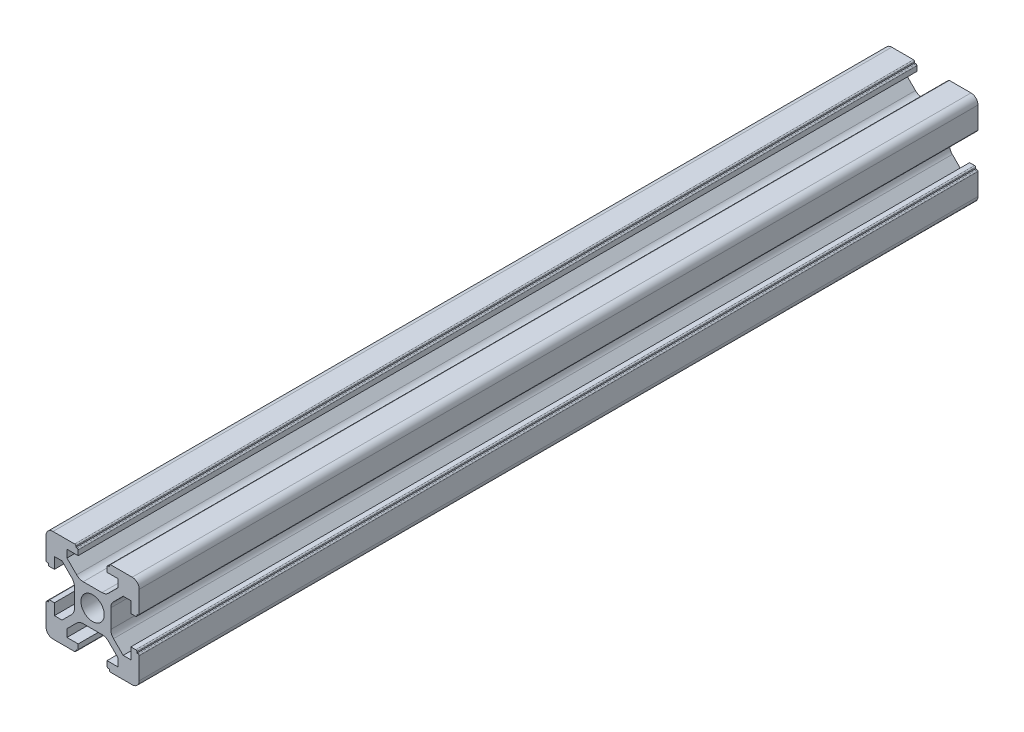
SolidWorks part; units mm, degrees
ref_plane "Front Plane" through (0, 0, 0) normal (0, 0, 1) x (1, 0, 0)
ref_plane "Top Plane" through (0, 0, 0) normal (0, 1, 0) x (1, 0, 0)
ref_plane "Right Plane" through (0, 0, 0) normal (1, 0, 0) x (0, 0, -1)
sketch "Sketch1" plane through (0, 0, 0) normal (0, 0, 1) x (1, 0, 0)
  line L0 (0, 0) -> (-10, 10) construction
  line L5 (0, 0) -> (10, 10) construction
  line L6 (22.7721, 0) -> (-22.7721, 0) construction
  line L7 (-8.5, 10) -> (-3.85, 10)
  line L8 (8.5, 10) -> (3.85, 10)
  line L9 (-3.6, 9.75) -> (-3.6, 9.5)
  line L10 (-3.6, 9.5) -> (-3.35, 9.5)
  line L11 (3.6, 9.75) -> (3.6, 9.5)
  line L12 (3.6, 9.5) -> (3.35, 9.5)
  line L13 (-3.1, 9.25) -> (-3.1, 8.2)
  line L14 (3.1, 9.25) -> (3.1, 8.2)
  line L15 (-3.1, 8.2) -> (-5.5, 8.2)
  line L16 (3.1, 8.2) -> (5.5, 8.2)
  line L17 (-3.4251, 4.4858) -> (-5.5, 6.5607)
  line L18 (-2.0109, 3.9) -> (2.0109, 3.9)
  line L19 (-5.5, 6.5607) -> (-5.5, 8.2)
  line L20 (5.5, 6.5607) -> (3.4251, 4.4858)
  line L21 (5.5, 6.5607) -> (5.5, 8.2)
  line L22 (10, 8.5) -> (10, 3.85)
  line L23 (10, -8.5) -> (10, -3.85)
  line L24 (9.75, 3.6) -> (9.5, 3.6)
  line L25 (9.5, 3.6) -> (9.5, 3.35)
  line L26 (9.75, -3.6) -> (9.5, -3.6)
  line L27 (9.5, -3.6) -> (9.5, -3.35)
  line L28 (9.25, 3.1) -> (8.2, 3.1)
  line L29 (9.25, -3.1) -> (8.2, -3.1)
  line L30 (8.2, 3.1) -> (8.2, 5.5)
  line L31 (8.2, -3.1) -> (8.2, -5.5)
  line L32 (4.4858, 3.4251) -> (6.5607, 5.5)
  line L33 (3.9, 2.0109) -> (3.9, -2.0109)
  line L34 (6.5607, 5.5) -> (8.2, 5.5)
  line L35 (6.5607, -5.5) -> (4.4858, -3.4251)
  line L36 (6.5607, -5.5) -> (8.2, -5.5)
  line L37 (8.5, -10) -> (3.85, -10)
  line L38 (-8.5, -10) -> (-3.85, -10)
  line L39 (3.6, -9.75) -> (3.6, -9.5)
  line L40 (3.6, -9.5) -> (3.35, -9.5)
  line L41 (-3.6, -9.75) -> (-3.6, -9.5)
  line L42 (-3.6, -9.5) -> (-3.35, -9.5)
  line L43 (3.1, -9.25) -> (3.1, -8.2)
  line L44 (-3.1, -9.25) -> (-3.1, -8.2)
  line L45 (3.1, -8.2) -> (5.5, -8.2)
  line L46 (-3.1, -8.2) -> (-5.5, -8.2)
  line L47 (3.4251, -4.4858) -> (5.5, -6.5607)
  line L48 (2.0109, -3.9) -> (-2.0109, -3.9)
  line L49 (5.5, -6.5607) -> (5.5, -8.2)
  line L50 (-5.5, -6.5607) -> (-3.4251, -4.4858)
  line L51 (-5.5, -6.5607) -> (-5.5, -8.2)
  line L52 (-10, -8.5) -> (-10, -3.85)
  line L53 (-10, 8.5) -> (-10, 3.85)
  line L54 (-9.75, -3.6) -> (-9.5, -3.6)
  line L55 (-9.5, -3.6) -> (-9.5, -3.35)
  line L56 (-9.75, 3.6) -> (-9.5, 3.6)
  line L57 (-9.5, 3.6) -> (-9.5, 3.35)
  line L58 (-9.25, -3.1) -> (-8.2, -3.1)
  line L59 (-9.25, 3.1) -> (-8.2, 3.1)
  line L60 (-8.2, -3.1) -> (-8.2, -5.5)
  line L61 (-8.2, 3.1) -> (-8.2, 5.5)
  line L62 (-4.4858, -3.4251) -> (-6.5607, -5.5)
  line L63 (-3.9, -2.0109) -> (-3.9, 2.0109)
  line L64 (-6.5607, -5.5) -> (-8.2, -5.5)
  line L65 (-6.5607, 5.5) -> (-4.4858, 3.4251)
  line L66 (-6.5607, 5.5) -> (-8.2, 5.5)
  circle A5 centre (0, 0) radius 2.5
  arc A6 (-8.5, -10) -> (-10, -8.5) centre (-8.5, -8.5) cw
  arc A7 (10, -8.5) -> (8.5, -10) centre (8.5, -8.5) cw
  arc A8 (8.5, 10) -> (10, 8.5) centre (8.5, 8.5) cw
  arc A9 (-8.5, 10) -> (-10, 8.5) centre (-8.5, 8.5) ccw
  arc A10 (-4.4858, -3.4251) -> (-3.9, -2.0109) centre (-5.9, -2.0109) ccw
  arc A11 (-2.0109, -3.9) -> (-3.4251, -4.4858) centre (-2.0109, -5.9) ccw
  arc A12 (3.4251, -4.4858) -> (2.0109, -3.9) centre (2.0109, -5.9) ccw
  arc A13 (3.9, -2.0109) -> (4.4858, -3.4251) centre (5.9, -2.0109) ccw
  arc A14 (4.4858, 3.4251) -> (3.9, 2.0109) centre (5.9, 2.0109) ccw
  arc A15 (3.4251, 4.4858) -> (2.0109, 3.9) centre (2.0109, 5.9) cw
  arc A16 (-3.4251, 4.4858) -> (-2.0109, 3.9) centre (-2.0109, 5.9) ccw
  arc A17 (-3.9, 2.0109) -> (-4.4858, 3.4251) centre (-5.9, 2.0109) ccw
  arc A18 (10, 3.85) -> (9.75, 3.6) centre (9.75, 3.85) cw
  arc A19 (9.5, 3.35) -> (9.25, 3.1) centre (9.25, 3.35) cw
  arc A20 (10, -3.85) -> (9.75, -3.6) centre (9.75, -3.85) ccw
  arc A21 (9.5, -3.35) -> (9.25, -3.1) centre (9.25, -3.35) ccw
  arc A22 (3.85, -10) -> (3.6, -9.75) centre (3.85, -9.75) cw
  arc A23 (3.1, -9.25) -> (3.35, -9.5) centre (3.35, -9.25) ccw
  arc A24 (-3.1, -9.25) -> (-3.35, -9.5) centre (-3.35, -9.25) cw
  arc A25 (-3.85, -10) -> (-3.6, -9.75) centre (-3.85, -9.75) ccw
  arc A26 (-10, -3.85) -> (-9.75, -3.6) centre (-9.75, -3.85) cw
  arc A27 (-9.25, -3.1) -> (-9.5, -3.35) centre (-9.25, -3.35) ccw
  arc A28 (-9.5, 3.35) -> (-9.25, 3.1) centre (-9.25, 3.35) ccw
  arc A29 (-10, 3.85) -> (-9.75, 3.6) centre (-9.75, 3.85) ccw
  arc A30 (-3.1, 9.25) -> (-3.35, 9.5) centre (-3.35, 9.25) ccw
  arc A31 (-3.85, 10) -> (-3.6, 9.75) centre (-3.85, 9.75) cw
  arc A32 (3.35, 9.5) -> (3.1, 9.25) centre (3.35, 9.25) ccw
  arc A33 (3.85, 10) -> (3.6, 9.75) centre (3.85, 9.75) ccw
  point P6 (-3.1, 9.5)
  point P7 (0, 0)
  point P28 (9.5, 3.1)
  point P46 (3.1, -9.5)
  point P63 (-9.5, -3.1)
  point P77 (0, 0)
  point P123 (-3.1, 9.5)
  point P126 (-3.6, 10)
  point P129 (3.1, 9.5)
  point P132 (3.6, 10)
  dimension "D1" = 45
  dimension "D4" = 7.2
  dimension "D2" = 5
  dimension "D13" = 1.5
  dimension "D14" = 2
  dimension "D15" = 0.25
  dimension "D3" = 20
  dimension "D5" = 0.5
  dimension "D6" = 6.2
  dimension "D7" = 1.8
  dimension "D8" = 11
  dimension "D9" = 0.75
  dimension "D10" = 6.1
  dimension "D11" = 0.75
  dimension "D12" = 4
extrude "Boss-Extrude1" add sketch "Sketch1" along normal blind 180
